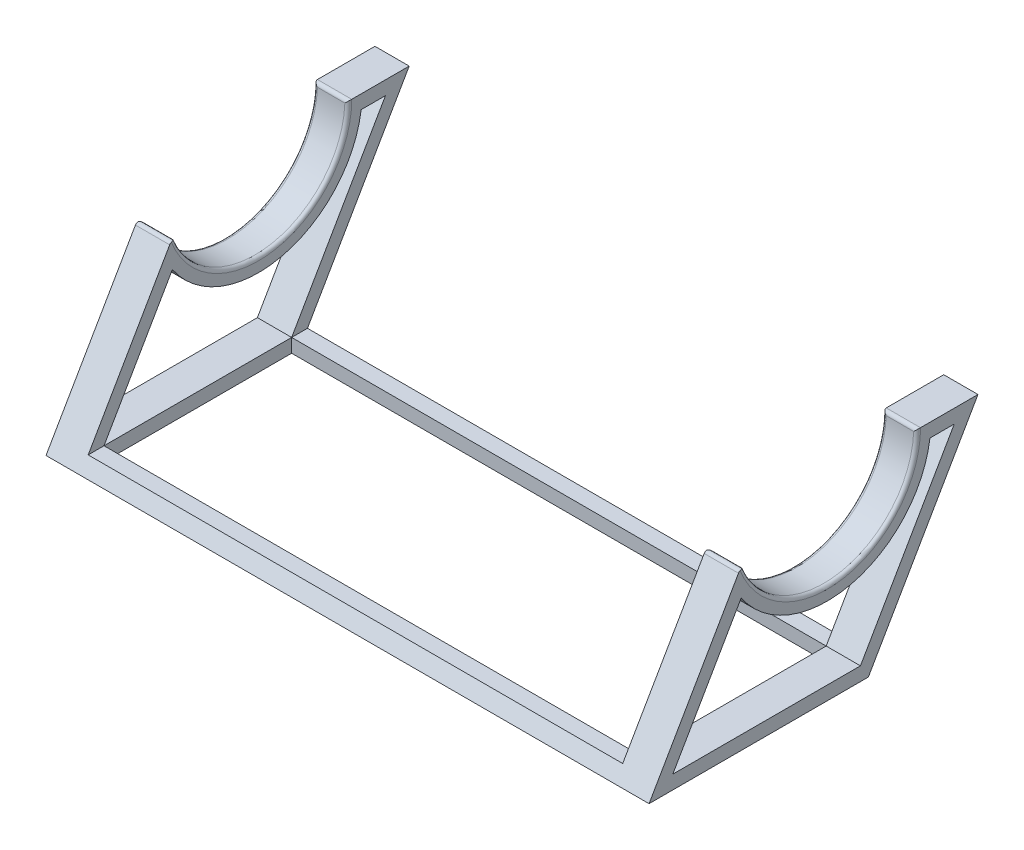
SolidWorks part; units mm, degrees
ref_plane "Front Plane" through (0, 0, 0) normal (0, 0, 1) x (1, 0, 0)
ref_plane "Top Plane" through (0, 0, 0) normal (0, 1, 0) x (1, 0, 0)
ref_plane "Right Plane" through (0, 0, 0) normal (1, 0, 0) x (0, 0, -1)
sketch "Sketch1" plane through (0, 0, 0) normal (1, 0, 0) x (0, 0, -1)
  line L0 (0, 0) -> (101.6, 0)
  line L10 (101.6, 0) -> (152.4, 87.9882)
  line L11 (152.4, 87.9882) -> (124.206, 87.9882)
  line L12 (43.0916, 74.6369) -> (0, 0)
  line L13 (141.4015, 81.6382) -> (130.1342, 81.6382)
  line L14 (97.9338, 6.35) -> (141.4015, 81.6382)
  line L15 (10.9985, 6.35) -> (97.9338, 6.35)
  line L16 (42.6879, 61.2377) -> (10.9985, 6.35)
  arc A1 (43.0916, 74.6369) -> (124.206, 87.9882) centre (82.55, 87.9882) ccw
  arc A2 (42.6879, 61.2377) -> (130.1342, 81.6382) centre (82.55, 87.9882) ccw
  dimension "D3" = 101.6
  dimension "D5" = 83.312
  dimension "D1" = 101.6
  dimension "D2" = 120
  dimension "D4" = 6.35
extrude "Boss-Extrude1" add sketch "Sketch1" along normal blind 279.4
sketch "Sketch2" plane through (0, 87.9882, 0) normal (0, 1, 0) x (1, 0, 0)
  line L0 (0, 152.4) -> (0, 124.206) construction
  line L1 (0, 152.4) -> (0, 124.206)
  line L2 (279.4, 152.4) -> (279.4, 124.206) construction
  line L3 (279.4, 152.4) -> (279.4, 124.206)
  line L4 (0, 152.4) -> (15.875, 152.4)
  line L5 (279.4, 152.4) -> (0, 152.4) construction
  line L6 (279.4, 0) -> (0, 0) construction
  line L7 (15.875, 152.4) -> (263.525, 152.4)
  line L8 (15.875, 152.4) -> (15.875, 0)
  line L9 (15.875, 0) -> (263.525, 0)
  line L10 (263.525, 152.4) -> (263.525, 0)
  line M7 (0, 124.206) -> (279.4, 124.206)
  line M9 (279.4, 152.4) -> (0, 152.4)
  dimension "D1" = 15.875
  dimension "D2" = 247.65
extrude "Cut-Extrude3" cut sketch "Sketch2" along direction (0, 1, 0) on the side against the normal up to vertex (81.6382 mm away) contours L10 L8 L9 M7 | L10 L8 M9 M7 region at (139.7, 87.9882, -138.303) region at (139.7, 87.9882, -62.103) up to point (279.4, 6.35, -10.9985)
fillet "Fillet1" radius 1.5875 8 edges at (0, 46.8853, -89.3155) (7.9375, 87.9882, -124.206) (15.875, 46.8853, -89.3155) (7.9375, 74.6369, -43.0916) (271.4625, 87.9882, -124.206) (279.4, 46.8853, -89.3155) (271.4625, 74.6369, -43.0916) (263.525, 46.8853, -89.3155)
sketch "Sketch4" plane through (0, 6.35, 0) normal (0, 1, 0) x (1, 0, 0)
  line L1 (263.525, 97.9338) -> (15.875, 97.9338)
  line L2 (263.525, 97.9338) -> (263.525, 10.9985)
  line L3 (263.525, 10.9985) -> (15.875, 10.9985)
  line L4 (15.875, 97.9338) -> (15.875, 10.9985)
extrude "Cut-Extrude5" cut sketch "Sketch4" against normal blind 6.35
